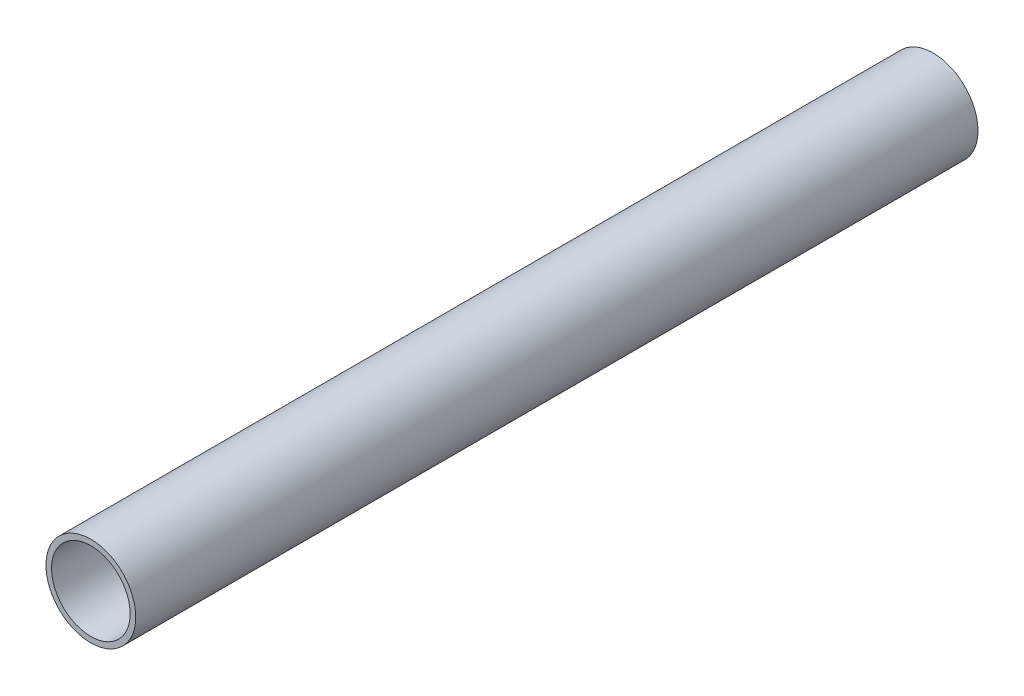
SolidWorks part; units mm, degrees
ref_plane "Front Plane" through (0, 0, 0) normal (0, 0, 1) x (1, 0, 0)
ref_plane "Top Plane" through (0, 0, 0) normal (0, 1, 0) x (1, 0, 0)
ref_plane "Right Plane" through (0, 0, 0) normal (1, 0, 0) x (0, 0, -1)
sketch "Sketch1" plane through (0, 0, 0) normal (0, 0, 1) x (1, 0, 0)
  circle A0 centre (0, 0) radius 8
  circle A1 centre (0, 0) radius 7
extrude "Boss-Extrude1" add sketch "Sketch1" along normal blind 150
ref_axis "Axis1" through (0, 0, 150) along (0, 0, -1)
